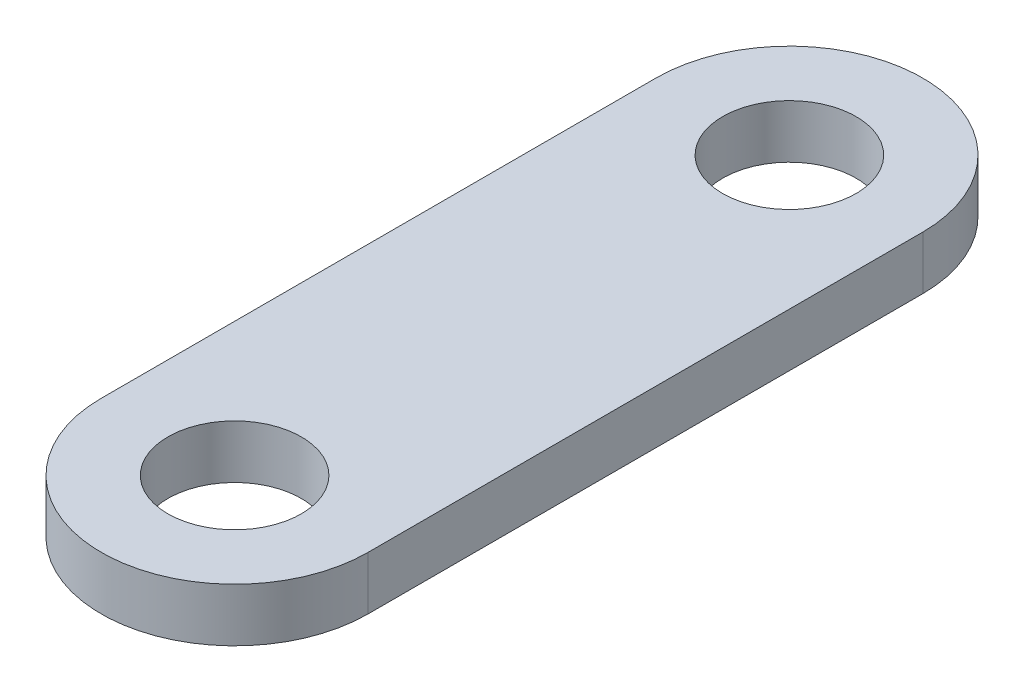
SolidWorks part; units mm, degrees
note: The reader was unsure of these and kept them because the rebuilt part matched: thickness of "Base-Flange1", "Sheet-Metal1".
material "Plain Carbon Steel"
ref_plane "Front Plane" through (0, 0, 0) normal (0, 0, 1) x (1, 0, 0)
ref_plane "Top Plane" through (0, 0, 0) normal (0, 1, 0) x (1, 0, 0)
ref_plane "Right Plane" through (0, 0, 0) normal (1, 0, 0) x (0, 0, -1)
sketch "Sketch1" plane through (0, 0, 0) normal (0, 1, 0) x (1, 0, 0)
  line L0 (0, -10.395) -> (0, 10.395) construction
  line L2 (5, -10.395) -> (5, 10.395)
  line L3 (-5, -10.395) -> (-5, 10.395)
  line L8 (-8, -3.75) -> (-5, 3.75) construction
  line L9 (-8, 3.75) -> (-5, -3.75) construction
  arc A0 (-5, -10.395) -> (5, -10.395) centre (0, -10.395) ccw
  arc A1 (5, 10.395) -> (-5, 10.395) centre (0, 10.395) ccw
  circle A2 centre (0, 10.395) radius 2.5
  circle A3 centre (0, -10.395) radius 2.5
  point P2 (0, 0)
  point P8 (-6.5, 0)
  dimension "D2" = 5
  dimension "D5" = 5
  dimension "D1" = 20.79
  dimension "D3" = 3
  dimension "D4" = 7.5
base flange "Base-Flange1" sketch "Sketch1" thickness 2 reverse thickness direction no parameters "D1"=3
ref_plane "Plane1" through (0, 6, 0) normal (0, 1, 0) x (1, 0, 0)
sketch "Bend-Lines1" [suppressed] plane through (0, 0, 0) normal (0, 1, 0) x (1, 0, 0)
sketch "Bounding-Box1" [suppressed] plane through (0, 0, 0) normal (0, 1, 0) x (1, 0, 0)
sheet metal parameters "Sheet-Metal1" thickness 2 parameters "D1"=3
flat pattern "Flat-Pattern1" [suppressed]
sketch "Bend-Lines2" plane through (0, 0, 0) normal (0, 1, 0) x (1, 0, 0)
sketch3d "Bounding-Box2" [suppressed]
  line L0 (-5, 25.7898, 0) -> (-5, -4.9998, 0) construction
  line L1 (5, 25.7898, 0) -> (5, -4.9998, 0) construction
  line L2 (-5, 25.7898, 0) -> (5, 25.7898, 0) construction
  line L3 (-5, -4.9998, 0) -> (5, -4.9998, 0) construction
